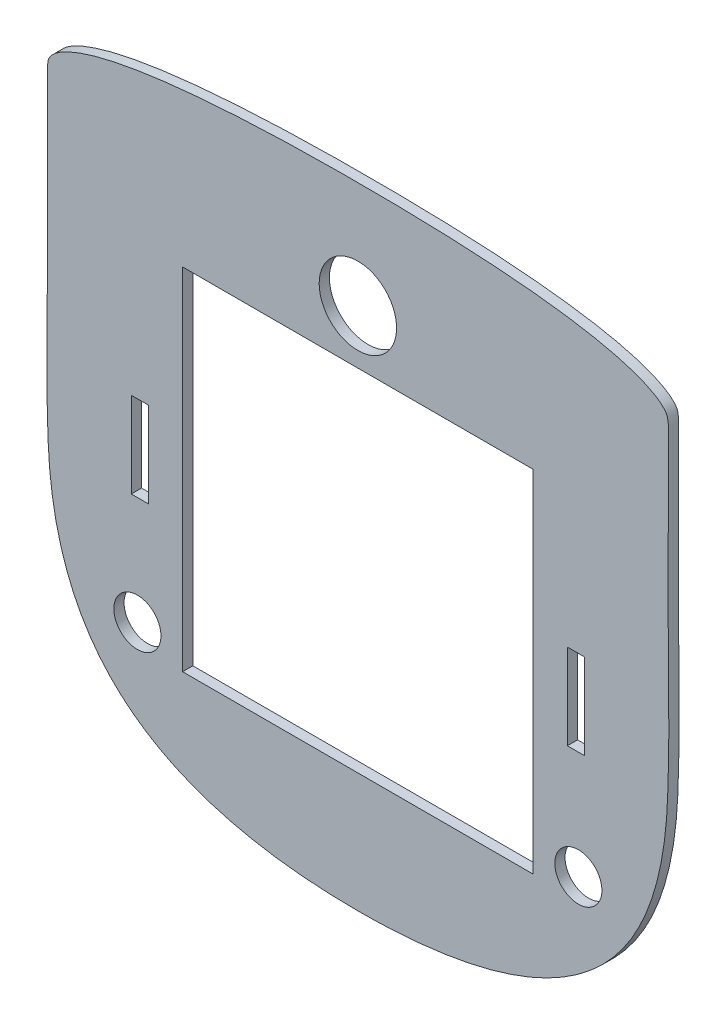
SolidWorks part; units mm, degrees
ref_plane "Front Plane" through (0, 0, 0) normal (0, 0, 1) x (1, 0, 0)
ref_plane "Top Plane" through (0, 0, 0) normal (0, 1, 0) x (1, 0, 0)
ref_plane "Right Plane" through (0, 0, 0) normal (1, 0, 0) x (0, 0, -1)
sketch "Sketch2" plane through (-0.2017, -72.2355, -2871.2971) normal (0, 0, 1) x (1, 0, 0)
  line L0 (52.07, 67.2522) -> (-52.07, 67.2522) construction
  line L1 (-52.07, 67.2522) -> (-52.07, -36.8878) construction
  line L2 (52.07, -36.8878) -> (52.07, 67.2522) construction
  line L3 (-52.07, -36.8878) -> (52.07, -36.8878) construction
  line L4 (52.07, 67.2522) -> (-52.07, 67.2522)
  line L5 (-52.07, 67.2522) -> (-52.07, -36.8878)
  line L6 (52.07, -36.8878) -> (52.07, 67.2522)
  line L7 (-52.07, -36.8878) -> (52.07, -36.8878)
  line L8 (0, 67.2522) -> (0, 47.5498)
  line L9 (-67.31, 26.6122) -> (-62.23, 26.6122)
  line L10 (-67.31, 26.6122) -> (-67.31, 1.2122)
  line L11 (-67.31, 1.2122) -> (-62.23, 1.2122)
  line L12 (-62.23, 26.6122) -> (-62.23, 1.2122)
  line L13 (67.31, 1.2122) -> (62.23, 1.2122)
  line L14 (67.31, 26.6122) -> (62.23, 26.6122)
  line L15 (62.23, 26.6122) -> (62.23, 1.2122)
  line L16 (67.31, 26.6122) -> (67.31, 1.2122)
  circle A0 centre (65.5, -30.8878) radius 7 construction
  circle A1 centre (-65.5, -30.8878) radius 7 construction
  circle A2 centre (0, 83.2872) radius 11.5 construction
  circle A3 centre (65.5, -30.8878) radius 7
  circle A4 centre (-65.5, -30.8878) radius 7
  circle A5 centre (0, 83.2872) radius 11.5
  spline S0 degree 3 poles (97.9117, 101.757) (98.0926, 100.5826) (98.1683, 99.8507) (98.201, 98.9643) (98.2056, 98.5204) (98.2033, 98.0762) (98.2036, 97.6318) (98.2026, 97.1872) (98.2018, 96.5942) (98.1997, 95.5557) (98.1964, 94.0701) (98.1912, 92.2844) (98.1853, 90.4955) (98.1786, 88.7035) (98.1713, 86.9085) (98.1636, 85.1105) (98.1554, 83.3094) (98.147, 81.5054) (98.1356, 79.096) (98.1213, 76.0769) (98.1051, 72.4424) (98.0908, 68.7965) (98.0796, 65.1394) (98.0728, 61.4713) (98.0711, 57.7925) (98.0753, 54.103) (98.0874, 50.4033) (98.1094, 46.6935) (98.1491, 41.7343) (98.2125, 35.5119) (98.2598, 28.01) (98.2502, 21.7312) (98.1939, 16.6943) (98.1345, 13.5409) (98.0699, 11.0154) (98.0125, 9.1199) (97.945, 7.2235) (97.8675, 5.3262) (97.778, 3.4282) (97.6786, 1.5298) (97.5624, -0.3688) (97.2739, -4.1659) (96.6367, -9.8576) (95.2643, -17.3922) (93.2832, -24.8169) (90.6142, -32.0401) (87.1877, -38.9585) (83.6766, -44.3599) (80.4862, -48.4025) (77.0545, -52.2409) (72.332, -56.6273) (66.103, -61.1882) (59.4287, -65.0467) (52.4324, -68.2445) (45.1957, -70.832) (37.7973, -72.8633) (30.2897, -74.3932) (22.7275, -75.4943) (12.6127, -76.4627) (5.0324, -76.7148) (-5.0355, -76.7148) (-12.6198, -76.4624) (-22.7388, -75.4931) (-30.3035, -74.391) (-37.8129, -72.8599) (-45.2125, -70.8272) (-52.4499, -68.238) (-59.4461, -65.0384) (-66.1196, -61.178) (-72.3471, -56.6154) (-77.0679, -52.2278) (-80.4981, -48.3887) (-83.6868, -44.3454) (-87.1957, -38.9438) (-90.6199, -32.0257) (-93.2868, -24.8034) (-95.2663, -17.38) (-96.6374, -9.847) (-97.2741, -4.1565) (-97.5622, -0.3603) (-97.6784, 1.5379) (-97.7779, 3.4359) (-97.8674, 5.3334) (-97.9449, 7.2303) (-98.0124, 9.1263) (-98.0698, 11.0213) (-98.1344, 13.5463) (-98.1939, 16.699) (-98.2502, 21.7349) (-98.2598, 28.0124) (-98.2124, 35.5129) (-98.1491, 41.7344) (-98.1094, 46.6929) (-98.0874, 50.4022) (-98.0753, 54.1015) (-98.0711, 57.7907) (-98.0728, 61.4693) (-98.0796, 65.1372) (-98.0908, 68.7942) (-98.1051, 72.44) (-98.1213, 76.0745) (-98.1356, 79.0937) (-98.147, 81.5032) (-98.1554, 83.3073) (-98.1636, 85.1085) (-98.1713, 86.9067) (-98.1786, 88.7018) (-98.1853, 90.494) (-98.1912, 92.283) (-98.1963, 94.069) (-98.1997, 95.5548) (-98.2018, 96.5934) (-98.2026, 97.1865) (-98.2036, 97.6312) (-98.2034, 98.0756) (-98.2056, 98.5199) (-98.201, 98.9639) (-98.1685, 99.8505) (-98.0927, 100.5825) (-97.9118, 101.7567) (-97.5911, 102.9272) (-96.7445, 104.5237) (-95.6284, 105.9307) (-94.3242, 107.1498) (-92.9089, 108.2104) (-90.9195, 109.4482) (-88.322, 110.7311) (-85.1289, 111.981) (-81.907, 113.0191) (-78.6797, 113.8993) (-75.4586, 114.6561) (-72.2483, 115.315) (-69.0513, 115.893) (-65.8677, 116.4036) (-62.6974, 116.856) (-59.5401, 117.2586) (-55.346, 117.7364) (-50.1305, 118.2378) (-43.9049, 118.7183) (-37.6983, 119.1001) (-31.4972, 119.4014) (-25.2861, 119.6319) (-19.0497, 119.8026) (-10.6783, 119.9573) (-4.3114, 120) (4.3116, 120) (10.6784, 119.9573) (19.0492, 119.8026) (25.285, 119.6319) (31.4954, 119.4014) (37.6957, 119.1003) (43.9016, 118.7185) (50.1264, 118.2381) (55.3414, 117.7368) (59.535, 117.2592) (62.6921, 116.8566) (65.8622, 116.4044) (69.0457, 115.8939) (72.2427, 115.316) (75.4529, 114.6572) (78.6742, 113.9005) (81.9018, 113.0204) (85.1241, 111.9825) (88.3177, 110.7327) (90.916, 109.4498) (92.906, 108.212) (94.3218, 107.1513) (95.6266, 105.9321) (96.7434, 104.5248) (97.5906, 102.9279) (97.9117, 101.757) (98.0926, 100.5826) (98.1683, 99.8507) knots -0.005356 -0.002678 0 0 0.002568 0.00321 0.003852 0.004494 0.005135 0.005777 0.006419 0.007703 0.010271 0.012839 0.015406 0.017974 0.020542 0.02311 0.025677 0.028245 0.030813 0.035948 0.041084 0.046219 0.051355 0.05649 0.061626 0.066761 0.071897 0.077032 0.082168 0.092439 0.10271 0.112981 0.118116 0.123252 0.125819 0.128387 0.130955 0.133522 0.13609 0.138658 0.141226 0.143793 0.154064 0.164335 0.174606 0.184877 0.195148 0.205419 0.210555 0.21569 0.225961 0.236232 0.246503 0.256774 0.267045 0.277316 0.287587 0.297858 0.308129 0.328671 0.328671 0.349207 0.359475 0.369743 0.380011 0.390279 0.400547 0.410816 0.421084 0.431352 0.44162 0.446754 0.451888 0.462156 0.472424 0.482692 0.492961 0.503229 0.513497 0.516064 0.518631 0.521198 0.523765 0.526332 0.528899 0.531466 0.534033 0.539167 0.544301 0.554569 0.564837 0.575105 0.580239 0.585374 0.590508 0.595642 0.600776 0.60591 0.611044 0.616178 0.621312 0.626446 0.629013 0.63158 0.634147 0.636714 0.639281 0.641848 0.644415 0.646982 0.649549 0.650833 0.651475 0.652116 0.652758 0.6534 0.654042 0.654683 0.65725 0.65725 0.659928 0.662606 0.665283 0.667961 0.670639 0.673317 0.678672 0.684027 0.689383 0.694738 0.700094 0.705449 0.710804 0.71616 0.721515 0.726871 0.732226 0.742937 0.753648 0.764359 0.775069 0.78578 0.796491 0.807202 0.828623 0.828623 0.850045 0.860757 0.871468 0.882179 0.89289 0.903601 0.914312 0.925023 0.930378 0.935734 0.941089 0.946445 0.9518 0.957156 0.962511 0.967867 0.973222 0.978578 0.983933 0.986611 0.989289 0.991967 0.994644 0.997322 1 1 1.002568 1.00321 1.003852 only from (98.0041, 101.1575) to (98.0041, 101.1575)
  spline S1 degree 3 poles (97.9117, 101.757) (98.0926, 100.5826) (98.1683, 99.8507) (98.201, 98.9643) (98.2056, 98.5204) (98.2033, 98.0762) (98.2036, 97.6318) (98.2026, 97.1872) (98.2018, 96.5942) (98.1997, 95.5557) (98.1964, 94.0701) (98.1912, 92.2844) (98.1853, 90.4955) (98.1786, 88.7035) (98.1713, 86.9085) (98.1636, 85.1105) (98.1554, 83.3094) (98.147, 81.5054) (98.1356, 79.096) (98.1213, 76.0769) (98.1051, 72.4424) (98.0908, 68.7965) (98.0796, 65.1394) (98.0728, 61.4713) (98.0711, 57.7925) (98.0753, 54.103) (98.0874, 50.4033) (98.1094, 46.6935) (98.1491, 41.7343) (98.2125, 35.5119) (98.2598, 28.01) (98.2502, 21.7312) (98.1939, 16.6943) (98.1345, 13.5409) (98.0699, 11.0154) (98.0125, 9.1199) (97.945, 7.2235) (97.8675, 5.3262) (97.778, 3.4282) (97.6786, 1.5298) (97.5624, -0.3688) (97.2739, -4.1659) (96.6367, -9.8576) (95.2643, -17.3922) (93.2832, -24.8169) (90.6142, -32.0401) (87.1877, -38.9585) (83.6766, -44.3599) (80.4862, -48.4025) (77.0545, -52.2409) (72.332, -56.6273) (66.103, -61.1882) (59.4287, -65.0467) (52.4324, -68.2445) (45.1957, -70.832) (37.7973, -72.8633) (30.2897, -74.3932) (22.7275, -75.4943) (12.6127, -76.4627) (5.0324, -76.7148) (-5.0355, -76.7148) (-12.6198, -76.4624) (-22.7388, -75.4931) (-30.3035, -74.391) (-37.8129, -72.8599) (-45.2125, -70.8272) (-52.4499, -68.238) (-59.4461, -65.0384) (-66.1196, -61.178) (-72.3471, -56.6154) (-77.0679, -52.2278) (-80.4981, -48.3887) (-83.6868, -44.3454) (-87.1957, -38.9438) (-90.6199, -32.0257) (-93.2868, -24.8034) (-95.2663, -17.38) (-96.6374, -9.847) (-97.2741, -4.1565) (-97.5622, -0.3603) (-97.6784, 1.5379) (-97.7779, 3.4359) (-97.8674, 5.3334) (-97.9449, 7.2303) (-98.0124, 9.1263) (-98.0698, 11.0213) (-98.1344, 13.5463) (-98.1939, 16.699) (-98.2502, 21.7349) (-98.2598, 28.0124) (-98.2124, 35.5129) (-98.1491, 41.7344) (-98.1094, 46.6929) (-98.0874, 50.4022) (-98.0753, 54.1015) (-98.0711, 57.7907) (-98.0728, 61.4693) (-98.0796, 65.1372) (-98.0908, 68.7942) (-98.1051, 72.44) (-98.1213, 76.0745) (-98.1356, 79.0937) (-98.147, 81.5032) (-98.1554, 83.3073) (-98.1636, 85.1085) (-98.1713, 86.9067) (-98.1786, 88.7018) (-98.1853, 90.494) (-98.1912, 92.283) (-98.1963, 94.069) (-98.1997, 95.5548) (-98.2018, 96.5934) (-98.2026, 97.1865) (-98.2036, 97.6312) (-98.2034, 98.0756) (-98.2056, 98.5199) (-98.201, 98.9639) (-98.1685, 99.8505) (-98.0927, 100.5825) (-97.9118, 101.7567) (-97.5911, 102.9272) (-96.7445, 104.5237) (-95.6284, 105.9307) (-94.3242, 107.1498) (-92.9089, 108.2104) (-90.9195, 109.4482) (-88.322, 110.7311) (-85.1289, 111.981) (-81.907, 113.0191) (-78.6797, 113.8993) (-75.4586, 114.6561) (-72.2483, 115.315) (-69.0513, 115.893) (-65.8677, 116.4036) (-62.6974, 116.856) (-59.5401, 117.2586) (-55.346, 117.7364) (-50.1305, 118.2378) (-43.9049, 118.7183) (-37.6983, 119.1001) (-31.4972, 119.4014) (-25.2861, 119.6319) (-19.0497, 119.8026) (-10.6783, 119.9573) (-4.3114, 120) (4.3116, 120) (10.6784, 119.9573) (19.0492, 119.8026) (25.285, 119.6319) (31.4954, 119.4014) (37.6957, 119.1003) (43.9016, 118.7185) (50.1264, 118.2381) (55.3414, 117.7368) (59.535, 117.2592) (62.6921, 116.8566) (65.8622, 116.4044) (69.0457, 115.8939) (72.2427, 115.316) (75.4529, 114.6572) (78.6742, 113.9005) (81.9018, 113.0204) (85.1241, 111.9825) (88.3177, 110.7327) (90.916, 109.4498) (92.906, 108.212) (94.3218, 107.1513) (95.6266, 105.9321) (96.7434, 104.5248) (97.5906, 102.9279) (97.9117, 101.757) (98.0926, 100.5826) (98.1683, 99.8507) knots -0.005356 -0.002678 0 0 0.002568 0.00321 0.003852 0.004494 0.005135 0.005777 0.006419 0.007703 0.010271 0.012839 0.015406 0.017974 0.020542 0.02311 0.025677 0.028245 0.030813 0.035948 0.041084 0.046219 0.051355 0.05649 0.061626 0.066761 0.071897 0.077032 0.082168 0.092439 0.10271 0.112981 0.118116 0.123252 0.125819 0.128387 0.130955 0.133522 0.13609 0.138658 0.141226 0.143793 0.154064 0.164335 0.174606 0.184877 0.195148 0.205419 0.210555 0.21569 0.225961 0.236232 0.246503 0.256774 0.267045 0.277316 0.287587 0.297858 0.308129 0.328671 0.328671 0.349207 0.359475 0.369743 0.380011 0.390279 0.400547 0.410816 0.421084 0.431352 0.44162 0.446754 0.451888 0.462156 0.472424 0.482692 0.492961 0.503229 0.513497 0.516064 0.518631 0.521198 0.523765 0.526332 0.528899 0.531466 0.534033 0.539167 0.544301 0.554569 0.564837 0.575105 0.580239 0.585374 0.590508 0.595642 0.600776 0.60591 0.611044 0.616178 0.621312 0.626446 0.629013 0.63158 0.634147 0.636714 0.639281 0.641848 0.644415 0.646982 0.649549 0.650833 0.651475 0.652116 0.652758 0.6534 0.654042 0.654683 0.65725 0.65725 0.659928 0.662606 0.665283 0.667961 0.670639 0.673317 0.678672 0.684027 0.689383 0.694738 0.700094 0.705449 0.710804 0.71616 0.721515 0.726871 0.732226 0.742937 0.753648 0.764359 0.775069 0.78578 0.796491 0.807202 0.828623 0.828623 0.850045 0.860757 0.871468 0.882179 0.89289 0.903601 0.914312 0.925023 0.930378 0.935734 0.941089 0.946445 0.9518 0.957156 0.962511 0.967867 0.973222 0.978578 0.983933 0.986611 0.989289 0.991967 0.994644 0.997322 1 1 1.002568 1.00321 1.003852 only from (98.0041, 101.1575) to (98.0041, 101.1575)
  dimension "D2" = 25.4
  dimension "D3" = 5.08
  dimension "D4" = 10.16
  dimension "D5" = 40.64
extrude "Boss-Extrude1" add sketch "Sketch2" along normal blind 3.048 contours L14 L16 L13 L15 L9 L12 L11 L10 L7 L5 L4 L6 A3 A4 A5 region at (-86.5368, -106.5692, -2871.2971)
sketch "Sketch8" plane through (0, 0, -2871.2971) normal (0, 0, -1) x (-1, 0, 0)
  spline S0 degree 3 poles (0.3104, -144.6233) (-3.2745, -144.6233) (-6.7385, -144.5374) (-13.6391, -144.1734) (-17.0759, -143.8967) (-23.9172, -143.1176) (-27.3217, -142.6152) (-34.0916, -141.3359) (-37.4568, -140.5583) (-42.4676, -139.1325) (-44.132, -138.6136) (-47.4451, -137.4763) (-49.0791, -136.8629) (-53.907, -134.8756) (-57.0275, -133.356) (-61.5302, -130.7241) (-63.0014, -129.7878) (-65.1579, -128.2838) (-65.8686, -127.7656) (-67.2588, -126.7056) (-67.9401, -126.1626) (-71.2775, -123.3816) (-73.7252, -120.9462) (-77.049, -116.9634) (-78.0997, -115.5815) (-79.5891, -113.4266) (-80.0721, -112.6932) (-81.0049, -111.2054) (-81.4532, -110.4536) (-83.6073, -106.6558) (-85.0532, -103.4958) (-86.8753, -98.6036) (-87.4246, -96.9473) (-88.1682, -94.4276) (-88.4026, -93.582) (-88.8431, -91.8912) (-89.0495, -91.0445) (-90.0179, -86.8057) (-90.5896, -83.3964) (-91.2148, -78.2615) (-91.3841, -76.5464) (-91.6545, -73.1101) (-91.754, -71.3887) (-91.898, -67.941) (-91.9539, -66.2157) (-92.0471, -62.7634) (-92.0825, -61.0363) (-92.2165, -52.3967) (-92.1817, -45.472) (-92.0888, -35.0908) (-92.0506, -31.6304) (-91.9891, -24.7096) (-91.9673, -21.2491) (-91.9354, -10.8677) (-91.9508, -3.9467) (-91.9892, 6.4348) (-92.0052, 9.8952) (-92.0303, 16.8162) (-92.042, 20.2767) (-92.0525, 24.1698) (-92.0537, 24.6023) (-92.0553, 25.2512) (-92.0564, 25.4675) (-92.0572, 25.9001) (-92.0571, 26.1163) (-92.027, 26.7631) (-91.9788, 27.1925) (-91.8893, 27.7273) (-91.8701, 27.8341) (-91.8289, 28.0477) (-91.8082, 28.1544) (-91.727, 28.4674) (-91.6523, 28.6684) (-91.4689, 29.0577) (-91.3594, 29.2474) (-91.118, 29.6064) (-90.9865, 29.7765) (-90.5682, 30.2665) (-90.2568, 30.5679) (-89.6014, 31.1295) (-89.2598, 31.3875) (-88.558, 31.8727) (-88.1978, 32.1002) (-87.0967, 32.7488) (-86.3351, 33.1358) (-84.7773, 33.8532) (-83.9869, 34.1795) (-81.6013, 35.0885) (-79.9866, 35.6037) (-76.7294, 36.5288) (-75.0863, 36.9373) (-71.7803, 37.6791) (-70.1172, 38.0123) (-66.7762, 38.6228) (-65.0971, 38.8997) (-61.7373, 39.4079) (-60.0554, 39.6394) (-55.0048, 40.2786) (-51.6313, 40.6319) (-44.8751, 41.2367) (-41.4925, 41.4873) (-31.334, 42.1214) (-24.5441, 42.3893) (-10.9746, 42.7178) (-4.1923, 42.7779) (9.3686, 42.7388) (16.1472, 42.6362) (29.6992, 42.2045) (36.4726, 41.8779) (46.6267, 41.1254) (50.0104, 40.83) (56.775, 40.1185) (60.1495, 39.7032) (66.8744, 38.6973) (70.2267, 38.1082) (75.2058, 37.0053) (76.8591, 36.5997) (80.1333, 35.6825) (81.7572, 35.1715) (84.146, 34.277) (84.9331, 33.958) (86.4814, 33.2608) (87.2446, 32.8832) (88.7241, 32.0392) (89.4378, 31.5786) (90.4316, 30.7738) (90.7488, 30.4866) (91.1842, 30.021) (91.3228, 29.8597) (91.5827, 29.5206) (91.7035, 29.3429) (91.9149, 28.9754) (92.0068, 28.785) (92.1183, 28.4865) (92.151, 28.3848) (92.2066, 28.1766) (92.2275, 28.0719) (92.3293, 27.5487) (92.3916, 27.129) (92.4435, 26.497) (92.4552, 26.286) (92.462, 25.8631) (92.4603, 25.6514) (92.4581, 25.0163) (92.4573, 24.5929) (92.4509, 22.4759) (92.446, 20.7824) (92.4295, 15.7018) (92.4176, 12.3147) (92.3895, 5.5405) (92.3758, 2.1534) (92.3457, -8.0078) (92.3404, -14.7819) (92.3933, -24.943) (92.4234, -28.33) (92.4902, -35.104) (92.5259, -38.491) (92.5994, -48.6509) (92.6051, -55.4224) (92.4234, -63.8791) (92.377, -65.57) (92.2618, -68.951) (92.1963, -70.6411) (91.8939, -75.7072) (91.5681, -79.0796) (90.8372, -84.1282) (90.5529, -85.8095) (89.8913, -89.1681) (89.5159, -90.8346) (88.2444, -95.7791) (87.2025, -99.0074) (85.2859, -103.7263) (84.588, -105.2785) (83.4426, -107.5724) (83.0436, -108.3327) (82.2145, -109.8346) (81.7857, -110.5738) (79.5701, -114.2106) (77.5707, -116.9323) (74.2241, -120.7274) (73.0499, -121.9439) (71.2012, -123.6964) (70.5705, -124.2686) (69.28, -125.389) (68.6186, -125.9384) (65.2622, -128.6077) (62.4266, -130.489) (57.9836, -132.9907) (56.4711, -133.7714) (54.1587, -134.8688) (53.3806, -135.2223) (51.8105, -135.9056) (51.0184, -136.2353) (47.0494, -137.8175) (43.8265, -138.8806) (37.3066, -140.6915) (34.0094, -141.4387) (27.3538, -142.6729) (23.9957, -143.1607) (18.92, -143.7292) (17.2207, -143.8913) (13.8228, -144.1646) (12.1227, -144.2762) (8.7203, -144.4525) (7.018, -144.5172) (4.4631, -144.5813) (3.1852, -144.6051) (1.6937, -144.6188) (0.9478, -144.6222) (0.6281, -144.6229) (0.4149, -144.6232) (0.3104, -144.6233) (-3.2745, -144.6233) (-6.7385, -144.5374) knots -0.000488 -0.000488 0 0 0.015625 0.015625 0.03125 0.03125 0.046875 0.046875 0.0625 0.0625 0.070312 0.070312 0.078125 0.078125 0.09375 0.09375 0.101562 0.101562 0.105469 0.105469 0.109375 0.109375 0.125 0.125 0.132812 0.132812 0.136719 0.136719 0.140625 0.140625 0.15625 0.15625 0.164062 0.164062 0.167969 0.167969 0.171875 0.171875 0.1875 0.1875 0.195312 0.195312 0.203125 0.203125 0.210937 0.210937 0.21875 0.21875 0.25 0.25 0.265625 0.265625 0.28125 0.28125 0.3125 0.3125 0.328125 0.328125 0.34375 0.34375 0.345703 0.345703 0.34668 0.34668 0.347656 0.347656 0.349609 0.349609 0.350098 0.350098 0.350586 0.350586 0.351563 0.351563 0.352539 0.352539 0.353516 0.353516 0.355469 0.355469 0.357422 0.357422 0.359375 0.359375 0.363281 0.363281 0.367187 0.367187 0.375 0.375 0.382812 0.382812 0.390625 0.390625 0.398437 0.398437 0.40625 0.40625 0.421875 0.421875 0.4375 0.4375 0.46875 0.46875 0.5 0.5 0.53125 0.53125 0.5625 0.5625 0.578125 0.578125 0.59375 0.59375 0.609375 0.609375 0.617187 0.617187 0.625 0.625 0.628906 0.628906 0.632812 0.632812 0.636719 0.636719 0.638672 0.638672 0.639648 0.639648 0.640625 0.640625 0.641602 0.641602 0.64209 0.64209 0.642578 0.642578 0.644531 0.644531 0.645508 0.645508 0.646484 0.646484 0.648437 0.648437 0.65625 0.65625 0.671875 0.671875 0.6875 0.6875 0.71875 0.71875 0.734375 0.734375 0.75 0.75 0.78125 0.78125 0.789063 0.789063 0.796875 0.796875 0.8125 0.8125 0.820313 0.820313 0.828125 0.828125 0.84375 0.84375 0.851563 0.851563 0.855469 0.855469 0.859375 0.859375 0.875 0.875 0.882813 0.882813 0.886719 0.886719 0.890625 0.890625 0.90625 0.90625 0.914063 0.914063 0.917969 0.917969 0.921875 0.921875 0.9375 0.9375 0.953125 0.953125 0.96875 0.96875 0.976563 0.976563 0.984375 0.984375 0.992188 0.992188 0.996094 0.998047 0.999023 0.999512 0.999512 1 1 1.015625 1.015625 1.03125 only from (0.2017, -144.6233) to (0.2017, -144.6233)
  spline S1 degree 3 poles (0.3104, -144.6233) (-3.2745, -144.6233) (-6.7385, -144.5374) (-13.6391, -144.1734) (-17.0759, -143.8967) (-23.9172, -143.1176) (-27.3217, -142.6152) (-34.0916, -141.3359) (-37.4568, -140.5583) (-42.4676, -139.1325) (-44.132, -138.6136) (-47.4451, -137.4763) (-49.0791, -136.8629) (-53.907, -134.8756) (-57.0275, -133.356) (-61.5302, -130.7241) (-63.0014, -129.7878) (-65.1579, -128.2838) (-65.8686, -127.7656) (-67.2588, -126.7056) (-67.9401, -126.1626) (-71.2775, -123.3816) (-73.7252, -120.9462) (-77.049, -116.9634) (-78.0997, -115.5815) (-79.5891, -113.4266) (-80.0721, -112.6932) (-81.0049, -111.2054) (-81.4532, -110.4536) (-83.6073, -106.6558) (-85.0532, -103.4958) (-86.8753, -98.6036) (-87.4246, -96.9473) (-88.1682, -94.4276) (-88.4026, -93.582) (-88.8431, -91.8912) (-89.0495, -91.0445) (-90.0179, -86.8057) (-90.5896, -83.3964) (-91.2148, -78.2615) (-91.3841, -76.5464) (-91.6545, -73.1101) (-91.754, -71.3887) (-91.898, -67.941) (-91.9539, -66.2157) (-92.0471, -62.7634) (-92.0825, -61.0363) (-92.2165, -52.3967) (-92.1817, -45.472) (-92.0888, -35.0908) (-92.0506, -31.6304) (-91.9891, -24.7096) (-91.9673, -21.2491) (-91.9354, -10.8677) (-91.9508, -3.9467) (-91.9892, 6.4348) (-92.0052, 9.8952) (-92.0303, 16.8162) (-92.042, 20.2767) (-92.0525, 24.1698) (-92.0537, 24.6023) (-92.0553, 25.2512) (-92.0564, 25.4675) (-92.0572, 25.9001) (-92.0571, 26.1163) (-92.027, 26.7631) (-91.9788, 27.1925) (-91.8893, 27.7273) (-91.8701, 27.8341) (-91.8289, 28.0477) (-91.8082, 28.1544) (-91.727, 28.4674) (-91.6523, 28.6684) (-91.4689, 29.0577) (-91.3594, 29.2474) (-91.118, 29.6064) (-90.9865, 29.7765) (-90.5682, 30.2665) (-90.2568, 30.5679) (-89.6014, 31.1295) (-89.2598, 31.3875) (-88.558, 31.8727) (-88.1978, 32.1002) (-87.0967, 32.7488) (-86.3351, 33.1358) (-84.7773, 33.8532) (-83.9869, 34.1795) (-81.6013, 35.0885) (-79.9866, 35.6037) (-76.7294, 36.5288) (-75.0863, 36.9373) (-71.7803, 37.6791) (-70.1172, 38.0123) (-66.7762, 38.6228) (-65.0971, 38.8997) (-61.7373, 39.4079) (-60.0554, 39.6394) (-55.0048, 40.2786) (-51.6313, 40.6319) (-44.8751, 41.2367) (-41.4925, 41.4873) (-31.334, 42.1214) (-24.5441, 42.3893) (-10.9746, 42.7178) (-4.1923, 42.7779) (9.3686, 42.7388) (16.1472, 42.6362) (29.6992, 42.2045) (36.4726, 41.8779) (46.6267, 41.1254) (50.0104, 40.83) (56.775, 40.1185) (60.1495, 39.7032) (66.8744, 38.6973) (70.2267, 38.1082) (75.2058, 37.0053) (76.8591, 36.5997) (80.1333, 35.6825) (81.7572, 35.1715) (84.146, 34.277) (84.9331, 33.958) (86.4814, 33.2608) (87.2446, 32.8832) (88.7241, 32.0392) (89.4378, 31.5786) (90.4316, 30.7738) (90.7488, 30.4866) (91.1842, 30.021) (91.3228, 29.8597) (91.5827, 29.5206) (91.7035, 29.3429) (91.9149, 28.9754) (92.0068, 28.785) (92.1183, 28.4865) (92.151, 28.3848) (92.2066, 28.1766) (92.2275, 28.0719) (92.3293, 27.5487) (92.3916, 27.129) (92.4435, 26.497) (92.4552, 26.286) (92.462, 25.8631) (92.4603, 25.6514) (92.4581, 25.0163) (92.4573, 24.5929) (92.4509, 22.4759) (92.446, 20.7824) (92.4295, 15.7018) (92.4176, 12.3147) (92.3895, 5.5405) (92.3758, 2.1534) (92.3457, -8.0078) (92.3404, -14.7819) (92.3933, -24.943) (92.4234, -28.33) (92.4902, -35.104) (92.5259, -38.491) (92.5994, -48.6509) (92.6051, -55.4224) (92.4234, -63.8791) (92.377, -65.57) (92.2618, -68.951) (92.1963, -70.6411) (91.8939, -75.7072) (91.5681, -79.0796) (90.8372, -84.1282) (90.5529, -85.8095) (89.8913, -89.1681) (89.5159, -90.8346) (88.2444, -95.7791) (87.2025, -99.0074) (85.2859, -103.7263) (84.588, -105.2785) (83.4426, -107.5724) (83.0436, -108.3327) (82.2145, -109.8346) (81.7857, -110.5738) (79.5701, -114.2106) (77.5707, -116.9323) (74.2241, -120.7274) (73.0499, -121.9439) (71.2012, -123.6964) (70.5705, -124.2686) (69.28, -125.389) (68.6186, -125.9384) (65.2622, -128.6077) (62.4266, -130.489) (57.9836, -132.9907) (56.4711, -133.7714) (54.1587, -134.8688) (53.3806, -135.2223) (51.8105, -135.9056) (51.0184, -136.2353) (47.0494, -137.8175) (43.8265, -138.8806) (37.3066, -140.6915) (34.0094, -141.4387) (27.3538, -142.6729) (23.9957, -143.1607) (18.92, -143.7292) (17.2207, -143.8913) (13.8228, -144.1646) (12.1227, -144.2762) (8.7203, -144.4525) (7.018, -144.5172) (4.4631, -144.5813) (3.1852, -144.6051) (1.6937, -144.6188) (0.9478, -144.6222) (0.6281, -144.6229) (0.4149, -144.6232) (0.3104, -144.6233) (-3.2745, -144.6233) (-6.7385, -144.5374) knots -0.000488 -0.000488 0 0 0.015625 0.015625 0.03125 0.03125 0.046875 0.046875 0.0625 0.0625 0.070312 0.070312 0.078125 0.078125 0.09375 0.09375 0.101562 0.101562 0.105469 0.105469 0.109375 0.109375 0.125 0.125 0.132812 0.132812 0.136719 0.136719 0.140625 0.140625 0.15625 0.15625 0.164062 0.164062 0.167969 0.167969 0.171875 0.171875 0.1875 0.1875 0.195312 0.195312 0.203125 0.203125 0.210937 0.210937 0.21875 0.21875 0.25 0.25 0.265625 0.265625 0.28125 0.28125 0.3125 0.3125 0.328125 0.328125 0.34375 0.34375 0.345703 0.345703 0.34668 0.34668 0.347656 0.347656 0.349609 0.349609 0.350098 0.350098 0.350586 0.350586 0.351563 0.351563 0.352539 0.352539 0.353516 0.353516 0.355469 0.355469 0.357422 0.357422 0.359375 0.359375 0.363281 0.363281 0.367187 0.367187 0.375 0.375 0.382812 0.382812 0.390625 0.390625 0.398437 0.398437 0.40625 0.40625 0.421875 0.421875 0.4375 0.4375 0.46875 0.46875 0.5 0.5 0.53125 0.53125 0.5625 0.5625 0.578125 0.578125 0.59375 0.59375 0.609375 0.609375 0.617187 0.617187 0.625 0.625 0.628906 0.628906 0.632812 0.632812 0.636719 0.636719 0.638672 0.638672 0.639648 0.639648 0.640625 0.640625 0.641602 0.641602 0.64209 0.64209 0.642578 0.642578 0.644531 0.644531 0.645508 0.645508 0.646484 0.646484 0.648437 0.648437 0.65625 0.65625 0.671875 0.671875 0.6875 0.6875 0.71875 0.71875 0.734375 0.734375 0.75 0.75 0.78125 0.78125 0.789063 0.789063 0.796875 0.796875 0.8125 0.8125 0.820313 0.820313 0.828125 0.828125 0.84375 0.84375 0.851563 0.851563 0.855469 0.855469 0.859375 0.859375 0.875 0.875 0.882813 0.882813 0.886719 0.886719 0.890625 0.890625 0.90625 0.90625 0.914063 0.914063 0.917969 0.917969 0.921875 0.921875 0.9375 0.9375 0.953125 0.953125 0.96875 0.96875 0.976563 0.976563 0.984375 0.984375 0.992188 0.992188 0.996094 0.998047 0.999023 0.999512 0.999512 1 1 1.015625 1.015625 1.03125 only from (0.2017, -144.6233) to (0.2017, -144.6233)
  spline S2 degree 3 poles (-97.8023, 28.922) (-97.8909, 28.3471) (-97.9665, 27.6153) (-97.9993, 26.7288) (-98.0038, 26.2849) (-98.0016, 25.8407) (-98.0019, 25.3963) (-98.0008, 24.9517) (-98, 24.3587) (-97.998, 23.3202) (-97.9946, 21.8347) (-97.9895, 20.0489) (-97.9836, 18.26) (-97.9769, 16.4681) (-97.9696, 14.6731) (-97.9618, 12.875) (-97.9537, 11.074) (-97.9452, 9.2699) (-97.9338, 6.8605) (-97.9195, 3.8415) (-97.9033, 0.207) (-97.889, -3.4389) (-97.8778, -7.096) (-97.871, -10.7641) (-97.8693, -14.443) (-97.8735, -18.1325) (-97.8857, -21.8322) (-97.9077, -25.5419) (-97.9474, -30.5011) (-98.0107, -36.7236) (-98.058, -44.2255) (-98.0485, -50.5042) (-97.9922, -55.5411) (-97.9327, -58.6945) (-97.8682, -61.2201) (-97.8107, -63.1155) (-97.7432, -65.012) (-97.6658, -66.9093) (-97.5763, -68.8072) (-97.4769, -70.7056) (-97.3606, -72.6043) (-97.0721, -76.4014) (-96.4349, -82.0931) (-95.0625, -89.6277) (-93.0815, -97.0524) (-90.4124, -104.2756) (-86.9859, -111.1939) (-83.4748, -116.5953) (-80.2845, -120.638) (-76.8527, -124.4764) (-72.1302, -128.8628) (-65.9013, -133.4237) (-59.2269, -137.2821) (-52.2307, -140.4799) (-44.9939, -143.0674) (-37.5956, -145.0987) (-30.088, -146.6286) (-22.5258, -147.7297) (-12.4109, -148.6982) (-4.8306, -148.9503) (5.2372, -148.9503) (12.8215, -148.6979) (22.9405, -147.7285) (30.5052, -146.6265) (38.0147, -145.0954) (45.4143, -143.0627) (52.6516, -140.4735) (59.6478, -137.2739) (66.3214, -133.4135) (72.5488, -128.8509) (77.2696, -124.4632) (80.6998, -120.6241) (83.8885, -116.5809) (87.3975, -111.1792) (90.8216, -104.2612) (93.4886, -97.0389) (95.468, -89.6155) (96.8392, -82.0824) (97.4758, -76.392) (97.764, -72.5958) (97.8801, -70.6976) (97.9796, -68.7996) (98.0691, -66.9021) (98.1466, -65.0052) (98.2141, -63.1092) (98.2716, -61.2142) (98.3362, -58.6892) (98.3956, -55.5365) (98.4519, -50.5006) (98.4615, -44.2231) (98.4142, -36.7225) (98.3508, -30.5011) (98.3112, -25.5425) (98.2891, -21.8333) (98.277, -18.1339) (98.2728, -14.4448) (98.2745, -10.7662) (98.2813, -7.0983) (98.2925, -3.4413) (98.3068, 0.2046) (98.323, 3.8391) (98.3373, 6.8582) (98.3487, 9.2677) (98.3571, 11.0719) (98.3653, 12.873) (98.3731, 14.6712) (98.3804, 16.4664) (98.387, 18.2585) (98.393, 20.0476) (98.3981, 21.8336) (98.4015, 23.3193) (98.4035, 24.358) (98.4043, 24.9511) (98.4053, 25.3957) (98.4051, 25.8402) (98.4074, 26.2845) (98.4027, 26.7284) (98.3702, 27.6151) (98.2944, 28.347) (98.1136, 29.5212) (97.7928, 30.6917) (96.9462, 32.2883) (95.8301, 33.6952) (94.5259, 34.9144) (93.1107, 35.9749) (91.1213, 37.2128) (88.5237, 38.4957) (85.3307, 39.7455) (82.1088, 40.7836) (78.8814, 41.6639) (75.6603, 42.4206) (72.4501, 43.0795) (69.253, 43.6575) (66.0694, 44.1682) (62.8991, 44.6205) (59.7418, 45.0231) (55.5478, 45.5009) (50.3322, 46.0023) (44.1066, 46.4828) (37.9, 46.8647) (31.6989, 47.1659) (25.4878, 47.3964) (19.2514, 47.5671) (10.88, 47.7218) (4.5131, 47.7645) (-4.1098, 47.7645) (-10.4766, 47.7218) (-18.8475, 47.5671) (-25.0833, 47.3964) (-31.2937, 47.166) (-37.494, 46.8648) (-43.6998, 46.483) (-49.9247, 46.0027) (-55.1396, 45.5013) (-59.3333, 45.0237) (-62.4904, 44.6212) (-65.6605, 44.1689) (-68.8439, 43.6584) (-72.0409, 43.0805) (-75.2512, 42.4217) (-78.4724, 41.6651) (-81.7001, 40.785) (-84.9224, 39.747) (-88.116, 38.4972) (-90.7142, 37.2144) (-92.7043, 35.9765) (-94.12, 34.9159) (-95.4248, 33.6966) (-96.5416, 32.2894) (-97.3889, 30.6924) (-97.71, 29.5215) (-97.8023, 28.922) (-97.8909, 28.3471) (-97.9665, 27.6153) knots -0.002678 0 0 0 0.002568 0.00321 0.003852 0.004494 0.005135 0.005777 0.006419 0.007703 0.010271 0.012839 0.015406 0.017974 0.020542 0.02311 0.025677 0.028245 0.030813 0.035948 0.041084 0.046219 0.051355 0.05649 0.061626 0.066761 0.071897 0.077032 0.082168 0.092439 0.10271 0.112981 0.118116 0.123252 0.125819 0.128387 0.130955 0.133522 0.13609 0.138658 0.141226 0.143793 0.154064 0.164335 0.174606 0.184877 0.195148 0.205419 0.210555 0.21569 0.225961 0.236232 0.246503 0.256774 0.267045 0.277316 0.287587 0.297858 0.308129 0.328671 0.328671 0.349207 0.359475 0.369743 0.380011 0.390279 0.400547 0.410816 0.421084 0.431352 0.44162 0.446754 0.451888 0.462156 0.472424 0.482692 0.492961 0.503229 0.513497 0.516064 0.518631 0.521198 0.523765 0.526332 0.528899 0.531466 0.534033 0.539167 0.544301 0.554569 0.564837 0.575105 0.580239 0.585374 0.590508 0.595642 0.600776 0.60591 0.611044 0.616178 0.621312 0.626446 0.629013 0.63158 0.634147 0.636714 0.639281 0.641848 0.644415 0.646982 0.649549 0.650833 0.651475 0.652116 0.652758 0.6534 0.654042 0.654683 0.65725 0.65725 0.659928 0.662606 0.665283 0.667961 0.670639 0.673317 0.678672 0.684027 0.689383 0.694738 0.700094 0.705449 0.710804 0.71616 0.721515 0.726871 0.732226 0.742937 0.753648 0.764359 0.775069 0.78578 0.796491 0.807202 0.828623 0.828623 0.850045 0.860757 0.871468 0.882179 0.89289 0.903601 0.914312 0.925023 0.930378 0.935734 0.941089 0.946445 0.9518 0.957156 0.962511 0.967867 0.973222 0.978578 0.983933 0.986611 0.989289 0.991967 0.994644 0.997322 1 1 1 1.002568 1.00321 1.003852 only from (-97.8023, 28.922) to (-97.8023, 28.922) construction
  spline S3 degree 3 poles (-97.8023, 28.922) (-97.8909, 28.3471) (-97.9665, 27.6153) (-97.9993, 26.7288) (-98.0038, 26.2849) (-98.0016, 25.8407) (-98.0019, 25.3963) (-98.0008, 24.9517) (-98, 24.3587) (-97.998, 23.3202) (-97.9946, 21.8347) (-97.9895, 20.0489) (-97.9836, 18.26) (-97.9769, 16.4681) (-97.9696, 14.6731) (-97.9618, 12.875) (-97.9537, 11.074) (-97.9452, 9.2699) (-97.9338, 6.8605) (-97.9195, 3.8415) (-97.9033, 0.207) (-97.889, -3.4389) (-97.8778, -7.096) (-97.871, -10.7641) (-97.8693, -14.443) (-97.8735, -18.1325) (-97.8857, -21.8322) (-97.9077, -25.5419) (-97.9474, -30.5011) (-98.0107, -36.7236) (-98.058, -44.2255) (-98.0485, -50.5042) (-97.9922, -55.5411) (-97.9327, -58.6945) (-97.8682, -61.2201) (-97.8107, -63.1155) (-97.7432, -65.012) (-97.6658, -66.9093) (-97.5763, -68.8072) (-97.4769, -70.7056) (-97.3606, -72.6043) (-97.0721, -76.4014) (-96.4349, -82.0931) (-95.0625, -89.6277) (-93.0815, -97.0524) (-90.4124, -104.2756) (-86.9859, -111.1939) (-83.4748, -116.5953) (-80.2845, -120.638) (-76.8527, -124.4764) (-72.1302, -128.8628) (-65.9013, -133.4237) (-59.2269, -137.2821) (-52.2307, -140.4799) (-44.9939, -143.0674) (-37.5956, -145.0987) (-30.088, -146.6286) (-22.5258, -147.7297) (-12.4109, -148.6982) (-4.8306, -148.9503) (5.2372, -148.9503) (12.8215, -148.6979) (22.9405, -147.7285) (30.5052, -146.6265) (38.0147, -145.0954) (45.4143, -143.0627) (52.6516, -140.4735) (59.6478, -137.2739) (66.3214, -133.4135) (72.5488, -128.8509) (77.2696, -124.4632) (80.6998, -120.6241) (83.8885, -116.5809) (87.3975, -111.1792) (90.8216, -104.2612) (93.4886, -97.0389) (95.468, -89.6155) (96.8392, -82.0824) (97.4758, -76.392) (97.764, -72.5958) (97.8801, -70.6976) (97.9796, -68.7996) (98.0691, -66.9021) (98.1466, -65.0052) (98.2141, -63.1092) (98.2716, -61.2142) (98.3362, -58.6892) (98.3956, -55.5365) (98.4519, -50.5006) (98.4615, -44.2231) (98.4142, -36.7225) (98.3508, -30.5011) (98.3112, -25.5425) (98.2891, -21.8333) (98.277, -18.1339) (98.2728, -14.4448) (98.2745, -10.7662) (98.2813, -7.0983) (98.2925, -3.4413) (98.3068, 0.2046) (98.323, 3.8391) (98.3373, 6.8582) (98.3487, 9.2677) (98.3571, 11.0719) (98.3653, 12.873) (98.3731, 14.6712) (98.3804, 16.4664) (98.387, 18.2585) (98.393, 20.0476) (98.3981, 21.8336) (98.4015, 23.3193) (98.4035, 24.358) (98.4043, 24.9511) (98.4053, 25.3957) (98.4051, 25.8402) (98.4074, 26.2845) (98.4027, 26.7284) (98.3702, 27.6151) (98.2944, 28.347) (98.1136, 29.5212) (97.7928, 30.6917) (96.9462, 32.2883) (95.8301, 33.6952) (94.5259, 34.9144) (93.1107, 35.9749) (91.1213, 37.2128) (88.5237, 38.4957) (85.3307, 39.7455) (82.1088, 40.7836) (78.8814, 41.6639) (75.6603, 42.4206) (72.4501, 43.0795) (69.253, 43.6575) (66.0694, 44.1682) (62.8991, 44.6205) (59.7418, 45.0231) (55.5478, 45.5009) (50.3322, 46.0023) (44.1066, 46.4828) (37.9, 46.8647) (31.6989, 47.1659) (25.4878, 47.3964) (19.2514, 47.5671) (10.88, 47.7218) (4.5131, 47.7645) (-4.1098, 47.7645) (-10.4766, 47.7218) (-18.8475, 47.5671) (-25.0833, 47.3964) (-31.2937, 47.166) (-37.494, 46.8648) (-43.6998, 46.483) (-49.9247, 46.0027) (-55.1396, 45.5013) (-59.3333, 45.0237) (-62.4904, 44.6212) (-65.6605, 44.1689) (-68.8439, 43.6584) (-72.0409, 43.0805) (-75.2512, 42.4217) (-78.4724, 41.6651) (-81.7001, 40.785) (-84.9224, 39.747) (-88.116, 38.4972) (-90.7142, 37.2144) (-92.7043, 35.9765) (-94.12, 34.9159) (-95.4248, 33.6966) (-96.5416, 32.2894) (-97.3889, 30.6924) (-97.71, 29.5215) (-97.8023, 28.922) (-97.8909, 28.3471) (-97.9665, 27.6153) knots -0.002678 0 0 0 0.002568 0.00321 0.003852 0.004494 0.005135 0.005777 0.006419 0.007703 0.010271 0.012839 0.015406 0.017974 0.020542 0.02311 0.025677 0.028245 0.030813 0.035948 0.041084 0.046219 0.051355 0.05649 0.061626 0.066761 0.071897 0.077032 0.082168 0.092439 0.10271 0.112981 0.118116 0.123252 0.125819 0.128387 0.130955 0.133522 0.13609 0.138658 0.141226 0.143793 0.154064 0.164335 0.174606 0.184877 0.195148 0.205419 0.210555 0.21569 0.225961 0.236232 0.246503 0.256774 0.267045 0.277316 0.287587 0.297858 0.308129 0.328671 0.328671 0.349207 0.359475 0.369743 0.380011 0.390279 0.400547 0.410816 0.421084 0.431352 0.44162 0.446754 0.451888 0.462156 0.472424 0.482692 0.492961 0.503229 0.513497 0.516064 0.518631 0.521198 0.523765 0.526332 0.528899 0.531466 0.534033 0.539167 0.544301 0.554569 0.564837 0.575105 0.580239 0.585374 0.590508 0.595642 0.600776 0.60591 0.611044 0.616178 0.621312 0.626446 0.629013 0.63158 0.634147 0.636714 0.639281 0.641848 0.644415 0.646982 0.649549 0.650833 0.651475 0.652116 0.652758 0.6534 0.654042 0.654683 0.65725 0.65725 0.659928 0.662606 0.665283 0.667961 0.670639 0.673317 0.678672 0.684027 0.689383 0.694738 0.700094 0.705449 0.710804 0.71616 0.721515 0.726871 0.732226 0.742937 0.753648 0.764359 0.775069 0.78578 0.796491 0.807202 0.828623 0.828623 0.850045 0.860757 0.871468 0.882179 0.89289 0.903601 0.914312 0.925023 0.930378 0.935734 0.941089 0.946445 0.9518 0.957156 0.962511 0.967867 0.973222 0.978578 0.983933 0.986611 0.989289 0.991967 0.994644 0.997322 1 1 1 1.002568 1.00321 1.003852 only from (-97.8023, 28.922) to (-97.8023, 28.922)
extrude "Cut-Extrude1" cut sketch "Sketch8" against normal blind 41.402
